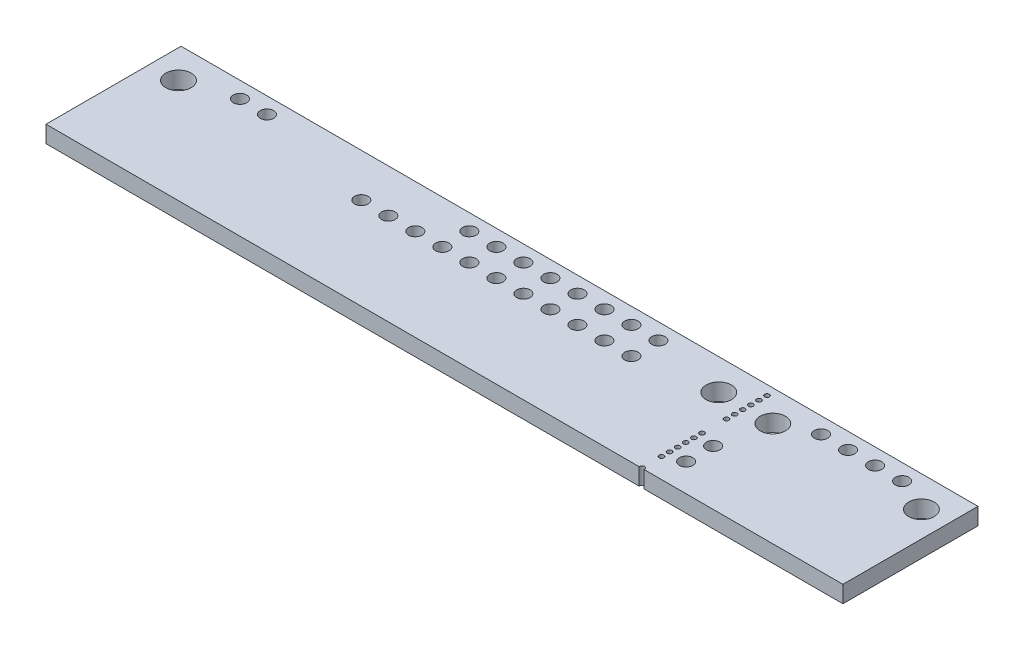
SolidWorks part; units mm, degrees
ref_plane "Front Plane" through (0, 0, 0) normal (0, 0, 1) x (1, 0, 0)
ref_plane "Top Plane" through (0, 0, 0) normal (0, 1, 0) x (1, 0, 0)
ref_plane "Right Plane" through (0, 0, 0) normal (1, 0, 0) x (0, 0, -1)
sketch "Sketch1" plane through (0, 0, 0) normal (0, 1, 0) x (1, 0, 0)
  line L1 (-132.7819, 20.3436) -> (-57.8519, 20.3436)
  line L2 (-132.7819, 20.3436) -> (-132.7819, 7.6436)
  line L3 (-132.7819, 7.6436) -> (-57.8519, 7.6436)
  line L4 (-57.8519, 20.3436) -> (-57.8519, 7.6436)
  dimension "D1" = 74.93
  dimension "D2" = 12.7
extrude "Boss-Extrude1" add sketch "Sketch1" along normal blind 1.5875
sketch "Sketch2" plane through (0, 1.5875, 0) normal (0, 1, 0) x (1, 0, 0)
  circle A0 centre (-130.1194, 17.4384) radius 1.1938
  circle A1 centre (-79.3194, 17.4384) radius 1.1938
  circle A2 centre (-74.2394, 17.4384) radius 1.1938
  circle A3 centre (-60.2694, 17.4384) radius 1.1938
  dimension "D1" = 2.3876
  dimension "D2" = 13.97
  dimension "D5" = 2.3876
  dimension "D6" = 2.3876
  dimension "D7" = 2.3876
  dimension "D3" = 69.85
  dimension "D4" = 50.8
extrude "Cut-Extrude1" cut sketch "Sketch2" against normal up to next
sketch "Sketch3" plane through (0, 0, 0) normal (0, -1, 0) x (1, 0, 0)
  line L0 (-127.912, -9.4362) -> (-127.412, -9.9362)
  line L2 (-130.112, -9.4362) -> (-127.912, -9.4362)
  line L3 (-130.112, -9.4362) -> (-130.112, -12.8362)
  line L4 (-130.112, -12.8362) -> (-127.412, -12.8362)
  line L5 (-127.412, -9.9362) -> (-127.412, -12.8362)
  point P3 (-127.412, -9.4362)
  point P6 (-128.762, -12.8362)
  dimension "D1" = 3.4
  dimension "D2" = 2.7
  dimension "D4" = 1.35
extrude "Boss-Extrude2" add sketch "Sketch3" along normal blind 1.6
sketch "Sketch4" plane through (0, -1.6, 0) normal (0, -1, 0) x (1, 0, 0)
  line L0 (-127.9376, -9.7412) -> (-127.6836, -9.9952)
  line L1 (-129.8426, -9.7412) -> (-127.9376, -9.7412)
  line L2 (-129.8426, -9.7412) -> (-129.8426, -11.0112)
  line L3 (-129.8426, -11.0112) -> (-127.6836, -11.0112)
  line L4 (-127.6836, -9.9952) -> (-127.6836, -11.0112)
  line L5 (-129.8426, -11.2612) -> (-127.6836, -11.2612)
  line L6 (-129.8426, -11.2612) -> (-129.8426, -12.5312)
  line L7 (-129.8426, -12.5312) -> (-127.6836, -12.5312)
  line L8 (-127.6836, -11.2612) -> (-127.6836, -12.5312)
  line L10 (-127.912, -9.4362) -> (-130.112, -9.4362) construction
  line L11 (-130.112, -12.8362) -> (-127.412, -12.8362) construction
  point P3 (-127.6836, -9.7412)
  dimension "D1" = 1.27
  dimension "D2" = 1.575
  dimension "D3" = 1.27
  dimension "D5" = 2.159
  dimension "D6" = 2.159
  dimension "D7" = 1.575
extrude "Cut-Extrude2" cut sketch "Sketch4" against normal blind 0.4
ref_axis "Axis1" through (-128.762, 0, -12.8362) along (0, -1, 0)
sketch "Sketch5" plane through (0, 0, -12.8362) normal (0, 0, -1) x (-1, 0, 0)
  line L0 (130.112, -0.7023) -> (130.3274, -0.7023)
  line L1 (130.112, -1.6) -> (130.112, 0) construction
  line L2 (130.3274, -0.7023) -> (130.6174, -0.2)
  line L3 (130.6174, -0.2) -> (131.112, -0.2)
  line L4 (131.112, -0.2) -> (131.112, 0)
  line L5 (57.8519, 0) -> (132.7819, 0) construction
  line L6 (131.112, 0) -> (130.502, 0)
  line L7 (130.502, 0) -> (130.212, -0.5023)
  line L8 (130.212, -0.5023) -> (130.112, -0.5023)
  line L9 (130.112, -0.5023) -> (130.112, -0.7023)
  line L10 (128.762, -1.6) -> (128.762, 0.2415) construction
  line L13 (130.112, -1.6) -> (127.412, -1.6) construction
  line L14 (128.762, 0) -> (128.762, -1.6) construction
  line L15 (127.412, -0.5023) -> (127.412, -0.7023)
  line L16 (127.312, -0.5023) -> (127.412, -0.5023)
  line L17 (127.022, 0) -> (127.312, -0.5023)
  line L18 (126.412, 0) -> (127.022, 0)
  line L19 (126.412, -0.2) -> (126.412, 0)
  line L20 (126.9065, -0.2) -> (126.412, -0.2)
  line L21 (127.1965, -0.7023) -> (126.9065, -0.2)
  line L22 (127.412, -0.7023) -> (127.1965, -0.7023)
  dimension "D1" = 0.2
  dimension "D2" = 0.2
  dimension "D3" = 0.61
  dimension "D4" = 1
  dimension "D5" = 0.2
  dimension "D6" = 120
  dimension "D7" = 0.1
extrude "Boss-Extrude3" add sketch "Sketch5" against normal blind 3.4
sketch "Sketch7" plane through (0, 0, 0) normal (0, -1, 0) x (1, 0, 0)
  line L0 (-130.112, -9.4362) -> (-130.112, -12.8362) construction
  line L1 (-131.7404, -8.6575) -> (-130.112, -8.6575)
  line L2 (-131.7404, -8.6575) -> (-131.7404, -9.9442)
  line L3 (-131.7404, -9.9442) -> (-130.112, -9.9442)
  line L4 (-130.112, -8.6575) -> (-130.112, -9.9442)
  line L5 (-127.412, -12.8362) -> (-127.412, -9.9362) construction
  line L6 (-125.532, -8.6658) -> (-127.412, -8.6658)
  line L7 (-125.532, -8.6658) -> (-125.532, -9.9442)
  line L8 (-125.532, -9.9442) -> (-127.412, -9.9442)
  line L9 (-127.412, -8.6658) -> (-127.412, -9.9442)
  line L10 (-127.412, -9.9362) -> (-127.412, -12.8362) construction
  line L11 (-131.7404, -13.1449) -> (-130.112, -13.1449)
  line L12 (-131.7404, -13.1449) -> (-131.7404, -12.2442)
  line L13 (-131.7404, -12.2442) -> (-130.112, -12.2442)
  line L14 (-130.112, -13.1449) -> (-130.112, -12.2442)
  line L15 (-125.532, -13.1449) -> (-127.412, -13.1449)
  line L16 (-125.532, -13.1449) -> (-125.532, -12.2442)
  line L17 (-125.532, -12.2442) -> (-127.412, -12.2442)
  line L18 (-127.412, -13.1449) -> (-127.412, -12.2442)
  line L19 (-127.912, -9.4362) -> (-130.112, -9.4362) construction
  line L20 (-131.7404, -10.4442) -> (-130.112, -10.4442)
  line L21 (-131.7404, -10.4442) -> (-131.7404, -11.7442)
  line L22 (-131.7404, -11.7442) -> (-130.112, -11.7442)
  line L23 (-130.112, -10.4442) -> (-130.112, -11.7442)
  line L24 (-125.532, -10.4442) -> (-127.412, -10.4442)
  line L25 (-125.532, -10.4442) -> (-125.532, -11.7442)
  line L26 (-125.532, -11.7442) -> (-127.412, -11.7442)
  line L27 (-127.412, -10.4442) -> (-127.412, -11.7442)
  dimension "D1" = 1.8
  dimension "D2" = 1.8
  dimension "D3" = 0.5
  dimension "D4" = 0
  dimension "D5" = 0
  dimension "D6" = 0
  dimension "D7" = 0
  dimension "D8" = 0
  dimension "D9" = 0.508
extrude "Cut-Extrude3" cut sketch "Sketch7" along normal through all
pattern_linear "LPattern1" count 8 spacing 9.525 along (1, 0, 0) of "Boss-Extrude2", "Cut-Extrude2", "Boss-Extrude3", "Cut-Extrude3"
sketch "Sketch8" plane through (0, 1.5875, 0) normal (0, 1, 0) x (1, 0, 0)
  circle A0 centre (-111.7759, 16.2833) radius 0.6333
  circle A1 centre (-109.2359, 16.2833) radius 0.6333
  circle A2 centre (-106.6959, 16.2833) radius 0.6333
  circle A3 centre (-104.1559, 16.2833) radius 0.6333
  circle A4 centre (-101.6159, 16.2833) radius 0.6333
  circle A5 centre (-99.0759, 16.2833) radius 0.6333
  circle A6 centre (-96.5359, 16.2833) radius 0.6333
  circle A7 centre (-93.9959, 16.2833) radius 0.6333
  circle A8 centre (-91.4559, 16.2833) radius 0.6333
  circle A9 centre (-88.9159, 16.2833) radius 0.6333
  circle A10 centre (-86.3759, 16.2833) radius 0.6333
  circle A11 centre (-104.1559, 18.8233) radius 0.6333
  circle A12 centre (-101.6159, 18.8233) radius 0.6333
  circle A13 centre (-99.0759, 18.8233) radius 0.6333
  circle A14 centre (-96.5359, 18.8233) radius 0.6333
  circle A15 centre (-93.9959, 18.8233) radius 0.6333
  circle A16 centre (-91.4559, 18.8233) radius 0.6333
  circle A17 centre (-88.9159, 18.8233) radius 0.6333
  circle A18 centre (-86.3759, 18.8233) radius 0.6333
  circle A19 centre (-71.0908, 18.8233) radius 0.6333
  circle A20 centre (-68.5508, 18.8233) radius 0.6333
  circle A21 centre (-66.0108, 18.8233) radius 0.6333
  circle A22 centre (-63.4708, 18.8233) radius 0.6333
  circle A23 centre (-125.723, 18.8233) radius 0.6333
  circle A24 centre (-123.183, 18.8233) radius 0.6333
  circle A25 centre (-75.2182, 12.8078) radius 0.6333
  circle A26 centre (-75.2182, 10.2678) radius 0.6333
  circle A27 centre (-76.7864, 15.6325) radius 0.2242
  circle A28 centre (-76.7864, 16.3945) radius 0.2242
  circle A29 centre (-76.7864, 17.1565) radius 0.2242
  circle A30 centre (-76.7864, 17.9185) radius 0.2242
  circle A31 centre (-76.7864, 18.6805) radius 0.2242
  circle A32 centre (-76.7864, 19.4425) radius 0.2242
  circle A33 centre (-76.7864, 9.5173) radius 0.2242
  circle A34 centre (-76.7864, 10.2793) radius 0.2242
  circle A35 centre (-76.7864, 11.0413) radius 0.2242
  circle A36 centre (-76.7864, 11.8033) radius 0.2242
  circle A37 centre (-76.7864, 12.5653) radius 0.2242
  circle A38 centre (-76.7864, 13.3273) radius 0.2242
  circle A39 centre (-76.7864, 7.6968) radius 0.2242
  dimension "D6" = 6
  dimension "D1" = 11
  dimension "D2" = 2
  dimension "D3" = 4
  dimension "D4" = 2
  dimension "D5" = 2
  dimension "D7" = 6
extrude "Cut-Extrude4" cut sketch "Sketch8" against normal up to next (1.5875 mm away)
equation "\"D2@Sketch4\"=.94mm + (\"D1@Sketch4\" /2)"
equation "\"D3@Sketch4\"=\"D1@Sketch4\""
equation "\"D6@Sketch4\"=\"D5@Sketch4\""
equation "\"D7@Sketch4\"=.94mm + (\"D1@Sketch4\"/2)"
equation "\"D4@Sketch3\"=\"D2@Sketch3\"/2"
